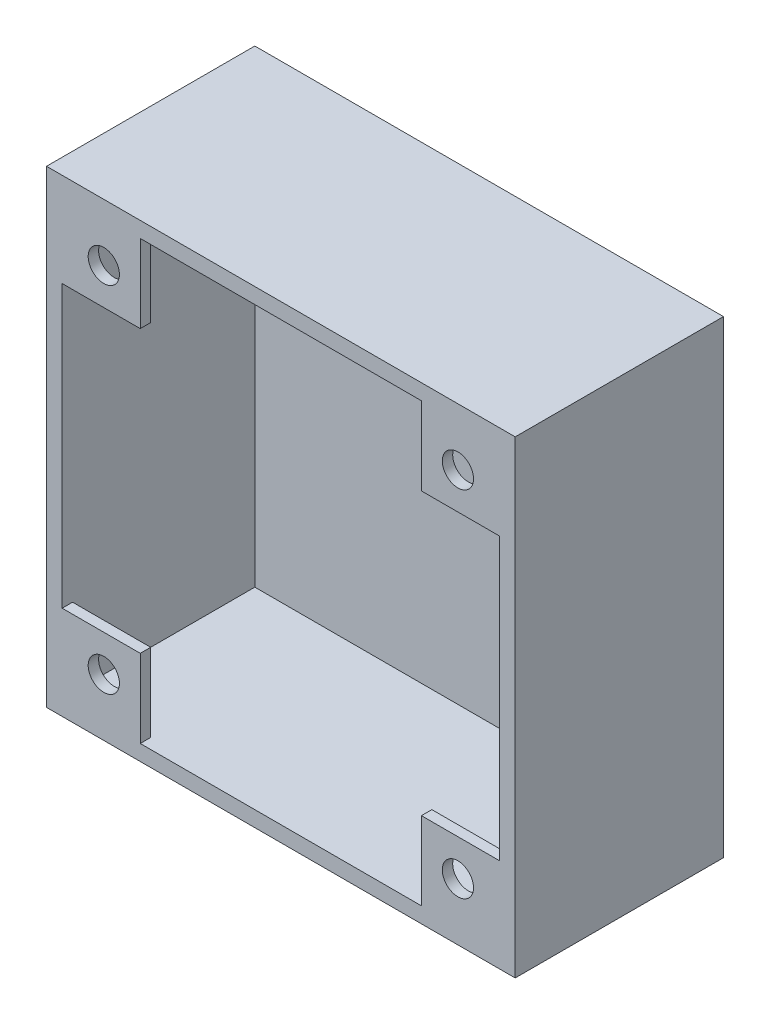
SolidWorks part; units mm, degrees
ref_plane "前视基准面" through (0, 0, 0) normal (0, 0, 1) x (1, 0, 0)
ref_plane "上视基准面" through (0, 0, 0) normal (0, 1, 0) x (1, 0, 0)
ref_plane "右视基准面" through (0, 0, 0) normal (1, 0, 0) x (0, 0, -1)
sketch "草图1" plane through (0, 0, 0) normal (0, 0, 1) x (1, 0, 0)
  line L1 (-45, 45) -> (45, 45)
  line L2 (-45, 45) -> (-45, -45)
  line L3 (-45, -45) -> (45, -45)
  line L4 (45, 45) -> (45, -45)
  line L5 (-45, 45) -> (45, -45) construction
  line L6 (-45, -45) -> (45, 45) construction
  point P0 (0, 0)
  dimension "D1" = 90
  dimension "D2" = 90
extrude "凸台-拉伸1" add sketch "草图1" along normal blind 40
shell "抽壳1" thickness 3 removed face at (0, 0, 40)
sketch "草图2" plane through (0, 0, 40) normal (0, 0, 1) x (1, 0, 0)
  line L0 (0, 0) -> (93.04, 0) construction
  line L1 (-42, 42) -> (-27, 42)
  line L2 (-42, 42) -> (-42, 27)
  line L3 (-42, 27) -> (-27, 27)
  line L4 (-27, 42) -> (-27, 27)
  line L5 (42, 42) -> (27, 42)
  line L6 (42, 42) -> (42, 27)
  line L7 (42, 27) -> (27, 27)
  line L8 (27, 42) -> (27, 27)
  line L9 (27, -42) -> (27, -27)
  line L10 (42, -27) -> (27, -27)
  line L11 (42, -42) -> (42, -27)
  line L12 (42, -42) -> (27, -42)
  line L13 (-27, -42) -> (-27, -27)
  line L14 (-42, -27) -> (-27, -27)
  line L15 (-42, -42) -> (-42, -27)
  line L16 (-42, -42) -> (-27, -42)
  dimension "D1" = 15
  dimension "D2" = 15
  dimension "D3" = 15
  dimension "D4" = 15
extrude "凸台-拉伸2" add sketch "草图2" against normal blind 2
sketch "草图3" plane through (0, 0, 40) normal (0, 0, 1) x (1, 0, 0)
  line L1 (0, 0) -> (0, 55.6478) construction
  line L2 (0, 0) -> (103.6974, 0) construction
  circle A0 centre (-34, 34) radius 3
  circle A1 centre (34, 34) radius 3
  circle A2 centre (34, -34) radius 3
  circle A3 centre (-34, -34) radius 3
  point P12 (0, 0)
  point P14 (0, 0)
  point P15 (0, 0)
  point P16 (0, 0)
  point P17 (0, 0)
  dimension "D3" = 6
  dimension "D4" = 6
  dimension "D5" = 6
  dimension "D6" = 6
  dimension "D1" = 68
  dimension "D2" = 68
extrude "切除-拉伸1" cut sketch "草图3" against normal up to next
